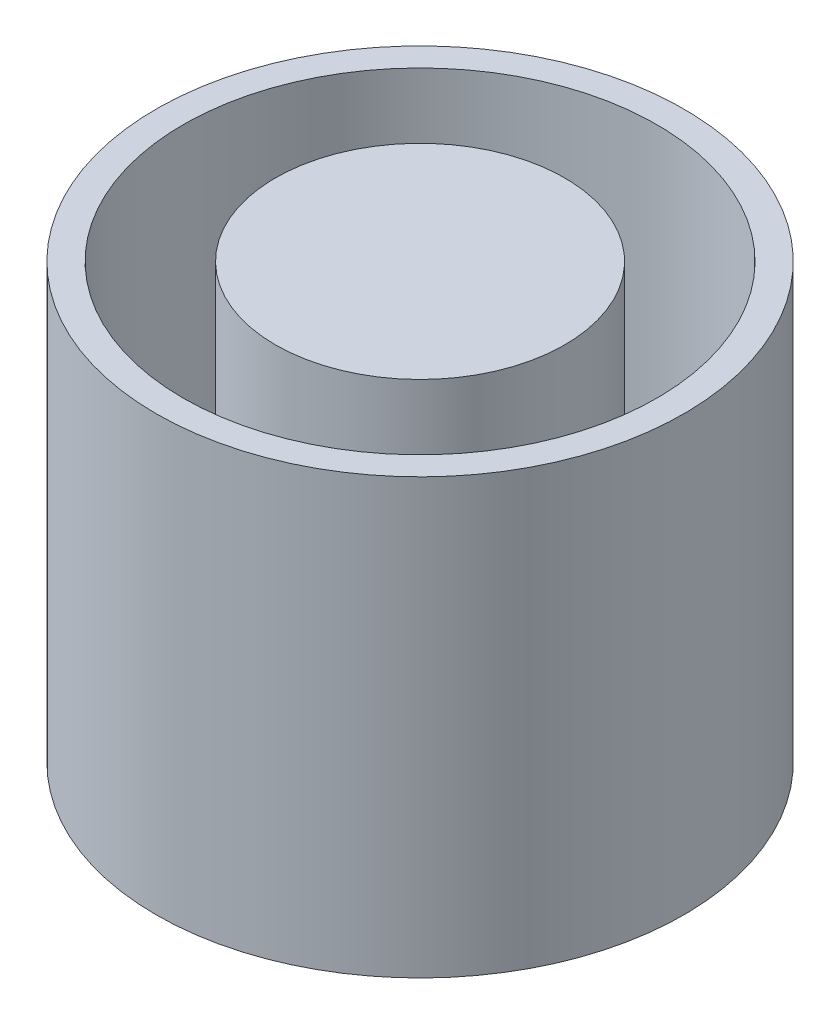
SolidWorks part; units mm, degrees
ref_plane "Plano frontal" through (0, 0, 0) normal (0, 0, 1) x (1, 0, 0)
ref_plane "Plano superior" through (0, 0, 0) normal (0, 1, 0) x (1, 0, 0)
ref_plane "Plano direito" through (0, 0, 0) normal (1, 0, 0) x (0, 0, -1)
sketch "Esboço1" plane through (0, 0, 0) normal (0, 1, 0) x (1, 0, 0)
  circle A0 centre (0, 0) radius 60.802
  circle A1 centre (0, 0) radius 54.5798
  circle A2 centre (0, 0) radius 33.3244
  circle A3 centre (0, 0) radius 14.0708
extrude "Ressalto-extrusão1" add sketch "Esboço1" along normal blind 100 contours A0 A1 | A2 A3 region at (-59.0823, 0, 0) region at (-32.3819, 0, 0)
sketch "Esboço3" plane through (0, 100, 0) normal (0, 1, 0) x (1, 0, 0)
  circle A0 centre (0, 0) radius 14.0708 construction
  circle A1 centre (0, 0) radius 14.0708
extrude "Ressalto-extrusão2" add sketch "Esboço3" against normal blind 10
extrude "Ressalto-extrusão3" add sketch "Esboço1<3>" along normal blind 10 contours A1 A2 region at (-53.036, 0, 0)
sketch "Esboço1<3>" plane through (0, 0, 0) normal (0, 1, 0) x (1, 0, 0) same geometry as "Esboço1"
